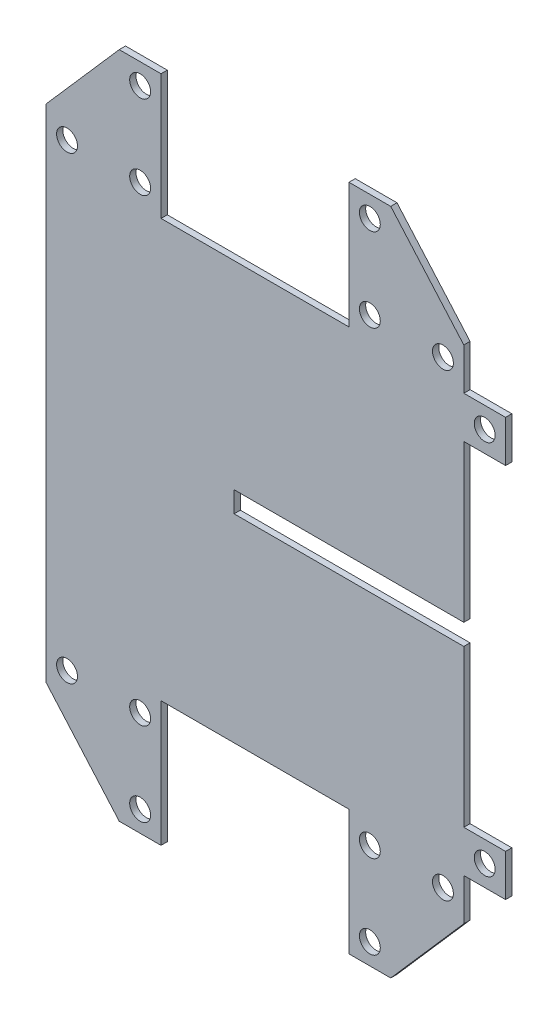
SolidWorks part; units mm, degrees
ref_plane "Plan de face" through (0, 0, 0) normal (0, 0, 1) x (1, 0, 0)
ref_plane "Plan de dessus" through (0, 0, 0) normal (0, 1, 0) x (1, 0, 0)
ref_plane "Plan de droite" through (0, 0, 0) normal (1, 0, 0) x (0, 0, -1)
sketch "Esquisse1" plane through (0, 0, 0) normal (0, 0, 1) x (1, 0, 0)
  line L0 (200, 80) -> (220, 100) construction
  line L1 (0, 100) -> (200, 100)
  line L2 (0, 100) -> (0, 0)
  line L3 (0, 0) -> (200, 0)
  line L4 (200, 100) -> (200, 0)
  line L5 (0, 100) -> (55, 100)
  line L6 (0, 100) -> (0, 160)
  line L7 (0, 160) -> (55, 160)
  line L8 (55, 100) -> (55, 160)
  line L9 (200, 100) -> (145, 100)
  line L10 (200, 100) -> (200, 160)
  line L11 (200, 160) -> (145, 160)
  line L12 (145, 100) -> (145, 160)
  line L13 (200, 0) -> (90, 0)
  line L14 (200, 0) -> (200, 5)
  line L15 (200, 5) -> (90, 5)
  line L16 (90, 0) -> (90, 5)
  line L17 (200, 100) -> (220, 100)
  line L18 (200, 100) -> (200, 80)
  line L19 (200, 80) -> (220, 80)
  line L20 (220, 100) -> (220, 80)
  line L21 (200, 120) -> (180, 120) construction
  line L22 (180, 120) -> (180, 100) construction
  line L23 (180, 120) -> (200, 100) construction
  line L24 (0, 120) -> (20, 120) construction
  line L25 (20, 120) -> (20, 100) construction
  line L26 (0, 100) -> (20, 120) construction
  line L27 (35, 160) -> (35, 100) construction
  line L28 (35, 140) -> (55, 140) construction
  line L29 (55, 120) -> (35, 120) construction
  line L30 (35, 160) -> (55, 140) construction
  line L31 (35, 120) -> (55, 100) construction
  line L32 (165, 160) -> (165, 100) construction
  line L33 (145, 140) -> (165, 140) construction
  line L34 (165, 120) -> (145, 120) construction
  line L35 (145, 160) -> (165, 140) construction
  line L36 (145, 120) -> (165, 100) construction
  line L37 (35, 160) -> (0, 120)
  line L38 (165, 160) -> (200, 120)
  line L39 (220, 100) -> (200, 120)
  line L40 (200, 5) -> (220, 80)
  circle A0 centre (210, 90) radius 5
  circle A1 centre (190, 110) radius 5
  circle A2 centre (10, 110) radius 5
  circle A3 centre (45, 150) radius 5
  circle A4 centre (45, 110) radius 5
  circle A5 centre (155, 150) radius 5
  circle A6 centre (155, 110) radius 5
  point P19 (210, 90)
  point P24 (190, 110)
  point P31 (10, 110)
  point P43 (45, 150)
  point P44 (45, 110)
  point P56 (155, 150)
  point P58 (155, 110)
  dimension "D9" = 10
  dimension "D10" = 10
  dimension "D14" = 10
  dimension "D18" = 10
  dimension "D19" = 10
  dimension "D21" = 10
  dimension "D22" = 10
  dimension "D1" = 200
  dimension "D2" = 100
  dimension "D3" = 90
  dimension "D4" = 60
  dimension "D5" = 110
  dimension "D6" = 5
  dimension "D7" = 20
  dimension "D8" = 20
  dimension "D11" = 20
  dimension "D12" = 20
  dimension "D13" = 20
  dimension "D15" = 20
  dimension "D16" = 20
  dimension "D17" = 20
  dimension "D20" = 20
extrude "Boss.-Extru.1" add sketch "Esquisse1" along normal blind 3 contours L7 L37 L6 L1 L8 A4 A3 A2 | L3 L16 L15 L4 L1 L2 | L38 L11 L12 L1 L10 A6 A5 A1 | L20 L17 L4 L19 A0 region at (31.6063, 125.73, 0) region at (98.7275, 51.3432, 0) region at (168.3937, 125.73, 0) region at (210, 99.7172, 0)
mirror "Symétrie1" about plane through (0, 0, 3) normal (0, 1, 0) of "Boss.-Extru.1"
